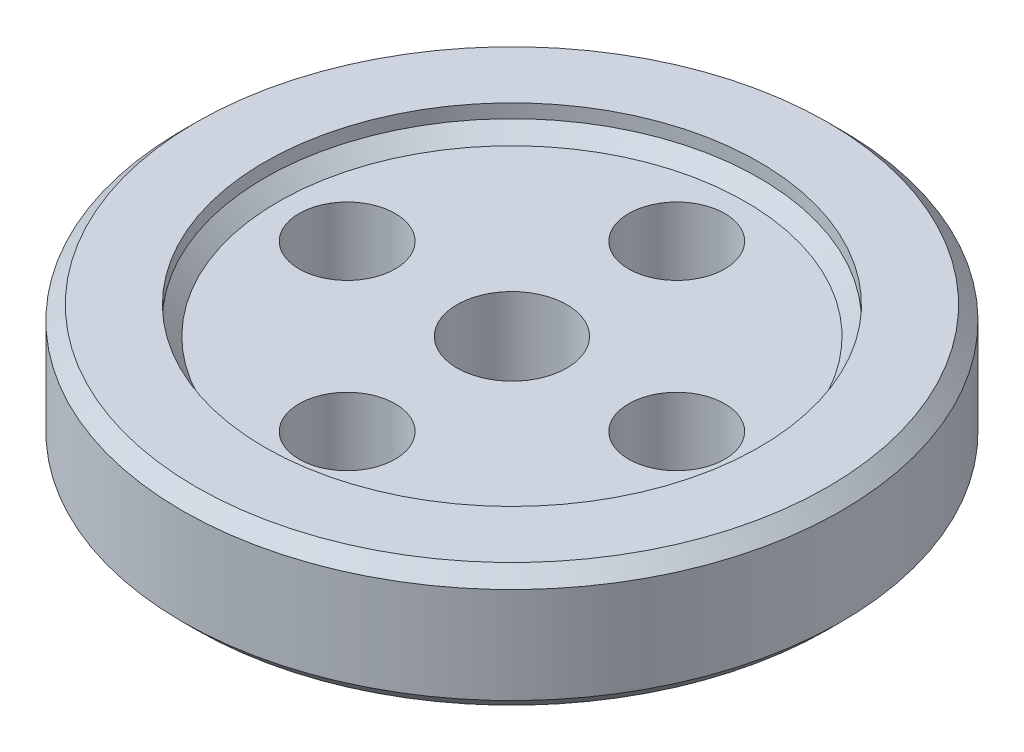
SolidWorks part; units mm, degrees
ref_plane "Front Plane" through (0, 0, 0) normal (0, 0, 1) x (1, 0, 0)
ref_plane "Top Plane" through (0, 0, 0) normal (0, 1, 0) x (1, 0, 0)
ref_plane "Right Plane" through (0, 0, 0) normal (1, 0, 0) x (0, 0, -1)
sketch "Sketch2" plane through (0, 0, 0) normal (0, 1, 0) x (1, 0, 0)
  circle A0 centre (0, 0) radius 16
  circle A1 centre (0, 0) radius 18
  circle A2 centre (0, 0) radius 24
  circle A4 centre (0, 0) radius 4
  circle A5 centre (0, 12) radius 3.5
  circle A6 centre (12, 0) radius 3.5
  circle A7 centre (0, -12) radius 3.5
  circle A8 centre (-12, 0) radius 3.5
  point P18 (0, 0)
  dimension "D1" = 48
  dimension "D2" = 36
  dimension "D3" = 32
  dimension "D4" = 7
  dimension "D5" = 8
  dimension "D7" = 4
extrude "Boss-Extrude2" add sketch "Sketch2" along normal blind 9 contours A2 A1 region at (-23.3212, 0, 0)
extrude "Boss-Extrude3" add sketch "Sketch2<3>" along normal blind 7 contours A1 A0 | A0 A8 A7 A6 A5 A4 region at (-15.5475, 0, 0) region at (-17.4909, 0, 0)
sketch "Sketch2<3>" plane through (0, 0, 0) normal (0, 1, 0) x (1, 0, 0) same geometry as "Sketch2"
chamfer "Chamfer1" distance 1 angle 45 2 edges at (0, 0, 24) (0, 9, 24)
chamfer "Chamfer3" distance 1 angle 45 1 edges at (0, 7, 18)
